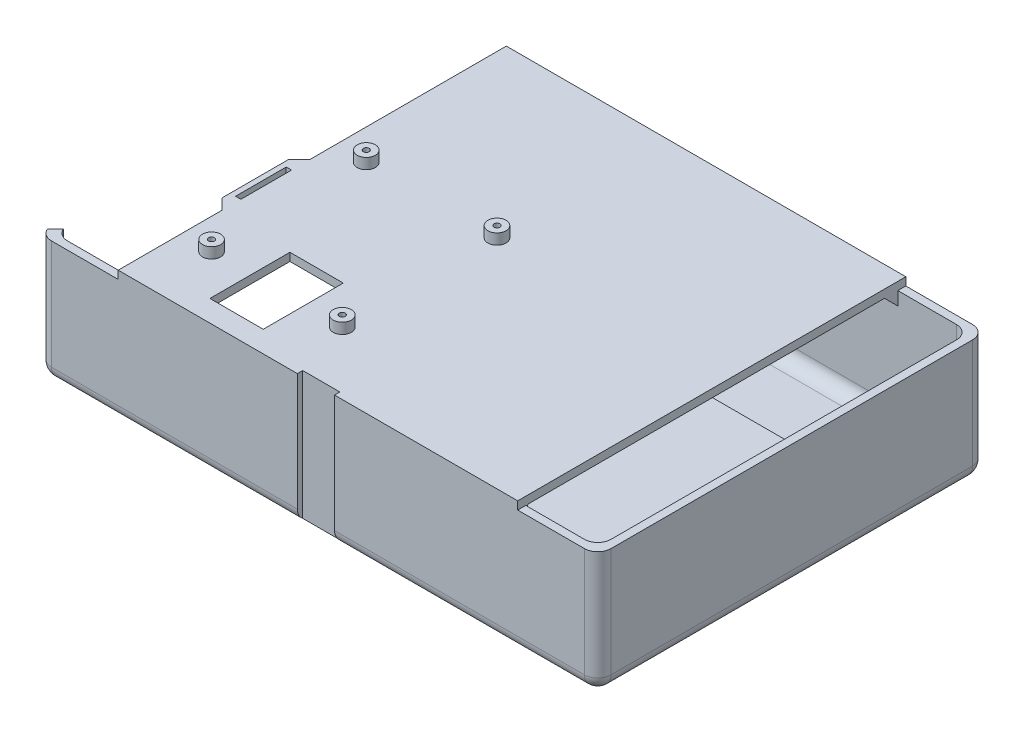
SolidWorks part; units mm, degrees
ref_plane "Front Plane" through (0, 0, 0) normal (0, 0, 1) x (1, 0, 0)
ref_plane "Top Plane" through (0, 0, 0) normal (0, 1, 0) x (1, 0, 0)
ref_plane "Right Plane" through (0, 0, 0) normal (1, 0, 0) x (0, 0, -1)
sketch "Sketch1" plane through (0, 0, 0) normal (0, 1, 0) x (1, 0, 0)
  line L1 (103.0685, -102.5392) -> (-106.7013, -102.5392)
  line L2 (103.0685, -102.5392) -> (103.0685, 42.9596)
  line L3 (103.0685, 42.9596) -> (-106.7013, 42.9596)
  line L4 (-106.7013, -102.5392) -> (-106.7013, 42.9596)
  line L6 (3.4026, -104.0392) -> (-8.5354, -104.0392) construction
  line L7 (-108.2013, -100.8421) -> (-108.2013, 38.9914) construction
  point P0 (0, 0)
  dimension "D1" = 1.5
  dimension "D2" = 1.5
extrude "Boss-Extrude1" add sketch "Sketch1" along normal blind 3
sketch "Sketch2" plane through (0, 3, 0) normal (0, 1, 0) x (1, 0, 0)
  line L4 (-106.7013, 42.9596) -> (-106.7013, -102.5392)
  line L5 (-106.7013, -102.5392) -> (103.0685, -102.5392)
  line L6 (103.0685, -102.5392) -> (103.0685, 42.9596)
  line L7 (103.0685, 42.9596) -> (-106.7013, 42.9596)
  line L8 (-106.7013, 42.9596) -> (-106.7013, -102.5392)
  line L9 (-106.7013, -102.5392) -> (103.0685, -102.5392)
  line L10 (103.0685, -102.5392) -> (103.0685, 42.9596)
  line L11 (103.0685, 42.9596) -> (-106.7013, 42.9596)
  line L16 (-103.7013, 39.9596) -> (-103.7013, -99.5392)
  line L17 (-103.7013, -99.5392) -> (100.0685, -99.5392)
  line L18 (100.0685, -99.5392) -> (100.0685, 39.9596)
  line L19 (100.0685, 39.9596) -> (-103.7013, 39.9596)
  line L20 (-103.7013, 39.9596) -> (-103.7013, -99.5392)
  line L21 (-103.7013, -99.5392) -> (100.0685, -99.5392)
  line L22 (100.0685, -99.5392) -> (100.0685, 39.9596)
  line L23 (100.0685, 39.9596) -> (-103.7013, 39.9596)
  dimension "D1" = 0
  dimension "D2" = 3
extrude "Boss-Extrude2" add sketch "Sketch2" along normal offset from surface (43 mm away) 20 offset beyond the face yes
sketch "Sketch3" plane through (-103.7013, 0, 0) normal (1, 0, 0) x (0, 0, -1)
  line L0 (39.9596, 46) -> (-99.5392, 46) construction
  line L1 (34.2109, 46) -> (-94.2682, 46)
  line L2 (34.2109, 46) -> (34.2109, 3)
  line L3 (34.2109, 3) -> (-94.2682, 3)
  line L4 (-94.2682, 46) -> (-94.2682, 3)
  line L5 (39.9596, 3) -> (-99.5392, 3) construction
extrude "Cut-Extrude1" cut sketch "Sketch3" against normal up to next
fillet "Fillet1" radius 5 8 edges at (100.0685, 24.5, 99.5392) (100.0685, 24.5, -39.9596) (-103.7013, 24.5, -39.9596) (-103.7013, 24.5, 99.5392) (103.0685, 23, -42.9596) (-106.7013, 23, -42.9596) (103.0685, 23, 102.5392) (-106.7013, 23, 102.5392)
fillet "Fillet2" radius 5 17 edges at (-103.7013, 3, 94.4037) (-102.2369, 3, 98.0748) (-1.8164, 3, 99.5392) (98.604, 3, 98.0748) (100.0685, 3, 29.7898) (98.604, 3, -38.4951) (-103.7013, 3, -34.5852) (-102.2369, 3, -38.4951) (-105.2369, 0, 101.0748) (-106.7013, 0, 29.7898) (-105.2369, 0, -41.4951) (-1.8164, 0, -42.9596) (101.604, 0, -41.4951) (103.0685, 0, 29.7898) (101.604, 0, 101.0748) (-1.8164, 3, -39.9596) (-1.8164, 0, 102.5392)
sketch "Sketch4" plane through (0, 46, 0) normal (0, 1, 0) x (1, 0, 0)
  line L0 (-101.7013, -102.5392) -> (98.0685, -102.5392) construction
  line L1 (-76.7013, -102.5392) -> (73.0685, -102.5392)
  line L2 (-76.7013, -102.5392) -> (-76.7013, 42.9596)
  line L3 (-76.7013, 42.9596) -> (73.0685, 42.9596)
  line L4 (73.0685, -102.5392) -> (73.0685, 42.9596)
  line L6 (98.0685, 42.9596) -> (-101.7013, 42.9596) construction
  line L7 (103.0685, -97.5392) -> (103.0685, 37.9596) construction
  line L8 (-106.7013, -94.2682) -> (-106.7013, -97.5392) construction
  dimension "D1" = 30
  dimension "D2" = 30
extrude "Boss-Extrude3" add sketch "Sketch4" along normal blind 3
sketch "Sketch6" plane through (0, 49, 0) normal (0, 1, 0) x (1, 0, 0)
  circle A0 centre (-16.2013, -79.0392) radius 1.4 construction
  circle A1 centre (-65.2013, -79.0392) radius 1.4 construction
  circle A2 centre (-16.2013, -21.0392) radius 1.4 construction
  circle A3 centre (-65.2013, -21.0392) radius 1.4 construction
  circle A4 centre (-16.2013, -79.0392) radius 1.4 construction
  circle A5 centre (-65.2013, -79.0392) radius 1.4 construction
  circle A6 centre (-16.2013, -21.0392) radius 1.4 construction
  circle A7 centre (-65.2013, -21.0392) radius 1.4 construction
  circle A8 centre (-65.2013, -21.0392) radius 3.4
  circle A9 centre (-65.2013, -79.0392) radius 3.4
  circle A10 centre (-16.2013, -21.0392) radius 3.4
  circle A11 centre (-16.2013, -79.0392) radius 3.4
  circle A12 centre (-65.2013, -21.0392) radius 1.1
  circle A13 centre (-16.2013, -21.0392) radius 1.1
  circle A14 centre (-65.2013, -79.0392) radius 1.1
  circle A15 centre (-16.2013, -79.0392) radius 1.1
  dimension "D2" = 2.2
  dimension "D3" = 2.2
  dimension "D4" = 2.2
  dimension "D5" = 2.2
  dimension "D1" = 2
extrude "Boss-Extrude4" add sketch "Sketch6" along normal up to surface (4 mm away)
sketch "Sketch7" plane through (0, 0, 0) normal (0, 1, 0) x (1, 0, 0)
  line L0 (-109.4507, 42.9596) -> (-106.8257, 40.3346)
  line L5 (-66.7013, 0.2102) -> (-66.7013, -59.7898)
  line L6 (-66.7013, -59.7898) -> (-99.0763, -92.1648)
  line L7 (-109.4507, -102.5392) -> (-109.4507, 42.9596)
  line L8 (-76.7013, 42.9596) -> (-76.7013, -102.5392) construction
  line L9 (-66.7013, -59.7898) -> (-66.7013, -102.5392) construction
  line L10 (-66.7013, -102.5392) -> (-109.4507, -102.5392) construction
  line L11 (-98.8263, 32.3352) -> (-66.7013, 0.2102)
  line L12 (-66.7013, 0.2102) -> (-66.7013, 42.9596) construction
  line L13 (-66.7013, 42.9596) -> (-109.4507, 42.9596) construction
  line L14 (-106.8257, 40.3346) -> (-98.8263, 32.3352)
  line L15 (-76.7013, 42.9596) -> (-101.7013, 42.9596) construction
  line L16 (-101.7013, -102.5392) -> (-76.7013, -102.5392) construction
  line L22 (-99.0763, -92.1648) -> (-107.0757, -100.1642)
  line L23 (-107.0757, -100.1642) -> (-109.4507, -102.5392)
  dimension "D1" = 45
  dimension "D2" = 45
  dimension "D3" = 10
  dimension "D4" = 60
extrude "Cut-Extrude3" cut sketch "Sketch7" along normal up to surface (46 mm away) up to face at (-1.8164, 46, 29.7898)
extrude "Cut-Extrude4" cut sketch "Sketch6<3>" against normal up to next contours A14 | A12 | A13 | A15 region at (-65.2013, 49, 21.0392) region at (-16.2013, 49, 21.0392) region at (-65.2013, 49, 79.0392) region at (-16.2013, 49, 79.0392)
sketch "Sketch6<3>" plane through (0, 49, 0) normal (0, 1, 0) x (1, 0, 0) same geometry as "Sketch6"
sketch "Sketch10" plane through (0, 0, 0) normal (0, 1, 0) x (1, 0, 0)
  line L0 (-9.5354, -102.5392) -> (-9.5354, -100.5392)
  line L1 (-76.7013, -102.5392) -> (73.0685, -102.5392) construction
  line L2 (-9.5354, -100.5392) -> (4.4026, -100.5392)
  line L3 (4.4026, -100.5392) -> (4.4026, -102.5392)
  line L4 (4.4026, -102.5392) -> (-9.5354, -102.5392)
  line L5 (-8.5354, -104.0392) -> (-8.5354, -105.7188) construction
  dimension "D1" = 1
  dimension "D2" = 1
  dimension "D3" = 2
extrude "Cut-Extrude7" cut sketch "Sketch10" along normal up to surface (49 mm away) up to face at (-16.2013, 49, 75.6392)
sketch "Sketch11" plane through (0, 49, 0) normal (0, 1, 0) x (1, 0, 0)
  line L0 (-76.7013, -35.5392) -> (-80.7013, -35.5392)
  line L1 (-76.7013, 42.9596) -> (-76.7013, -102.5392) construction
  line L2 (-80.7013, -35.5392) -> (-80.7013, -58.5392)
  line L3 (-80.7013, -58.5392) -> (-76.7013, -58.5392)
  line L4 (-76.7013, -58.5392) -> (-76.7013, -56.5392)
  line L5 (-76.7013, -56.5392) -> (-78.7013, -56.5392)
  line L6 (-78.7013, -56.5392) -> (-78.7013, -37.5392)
  line L7 (-78.7013, -37.5392) -> (-76.7013, -37.5392)
  line L8 (-76.7013, -37.5392) -> (-76.7013, -35.5392)
  line L9 (-20.7013, -82.5392) -> (-60.7013, -82.5392) construction
  dimension "D1" = 2
  dimension "D2" = 2
  dimension "D3" = 2
  dimension "D4" = 19
  dimension "D5" = 2
  dimension "D6" = 26
extrude "Boss-Extrude7" add sketch "Sketch11" against normal up to surface (3 mm away) up to face at (-16.2013, 46, 77.9392)
chamfer "Chamfer2" distance 5 angle 45 2 edges at (-76.7013, 47.5, 35.5392) (-76.7013, 47.5, 58.5392)
sketch "Sketch12" plane through (100.0685, 0, 0) normal (-1, 0, 0) x (0, 0, 1)
  line L0 (14.5392, 3) -> (14.5392, 31)
  line L1 (14.5392, 31) -> (99.5392, 31)
  line L2 (99.5392, 46) -> (99.5392, 8) construction
  line L3 (94.5392, 3) -> (-34.9596, 3) construction
  line L4 (94.5392, 3) -> (14.5392, 3) construction
  line L5 (99.5392, 8) -> (99.5392, 31) construction
  line L6 (17.5392, 3) -> (17.5392, 28)
  line L7 (17.5392, 28) -> (99.5392, 28)
  line L8 (17.5392, 3) -> (14.5392, 3)
  line L9 (99.5392, 28) -> (99.5392, 31)
  arc A0 (94.5392, 3) -> (99.5392, 8) centre (94.5392, 8) ccw construction
  arc A1 (94.5392, 3) -> (99.5392, 8) centre (94.5392, 8) ccw construction
  dimension "D2" = 82
  dimension "D3" = 25
  dimension "D1" = 3
extrude "Boss-Extrude8" add sketch "Sketch12" along normal up to surface (166.7698 mm away) up to face at (-66.7013, 1.5, 29.7898)
sketch "Sketch13" plane through (0, 0, -42.9596) normal (0, 0, -1) x (-1, 0, 0)
  line L0 (76.7013, 46) -> (106.3334, 46)
  line L1 (106.3334, 46) -> (106.3334, 0)
  line L2 (106.3334, 0) -> (76.7013, 46)
extrude "Cut-Extrude8" cut sketch "Sketch13" against normal up to next
chamfer "Chamfer3" distance 5 angle 45 1 edges at (-1.8164, 46, -39.9596)
chamfer "Chamfer4" distance 1 angle 45 1 edges at (-1.8164, 46, 99.5392)
sketch "Sketch14" plane through (0, 49, 0) normal (0, 1, 0) x (1, 0, 0)
  line L0 (95.0685, -99.5392) -> (-98.7013, -99.5392) construction
  line L1 (-50.3226, -94.5392) -> (-30.3226, -94.5392)
  line L2 (-50.3226, -94.5392) -> (-50.3226, -64.5392)
  line L3 (-50.3226, -64.5392) -> (-30.3226, -64.5392)
  line L4 (-30.3226, -94.5392) -> (-30.3226, -64.5392)
  dimension "D1" = 5
  dimension "D2" = 20
  dimension "D3" = 30
extrude "Cut-Extrude9" cut sketch "Sketch14" against normal up to surface (21 mm away) up to face at (32.5677, 28, 65.9463)
chamfer "Chamfer5" distance 2 angle 45 6 edges at (100.0685, 31, 54.5392) (98.604, 31, 98.0748) (14.1836, 31, 99.5392) (100.0685, 19.5, 14.5392) (98.604, 4.4645, 14.5392) (14.1836, 3, 14.5392)
sketch "Sketch16" plane through (0, 31, 0) normal (0, 1, 0) x (1, 0, 0)
  line L5 (-50.3226, -94.5392) -> (-66.7013, -94.5392)
  line L6 (-66.7013, -97.5392) -> (-66.7013, -14.5392) construction
  line L7 (-66.7013, -94.5392) -> (-66.7013, -28.1605)
  line L8 (-66.7013, -28.1605) -> (-30.3226, -64.5392)
  line L9 (-30.3226, -64.5392) -> (-50.3226, -64.5392)
  line L10 (-50.3226, -64.5392) -> (-50.3226, -94.5392)
  dimension "D1" = 45
extrude "Cut-Extrude11" cut sketch "Sketch16" against normal up to next
